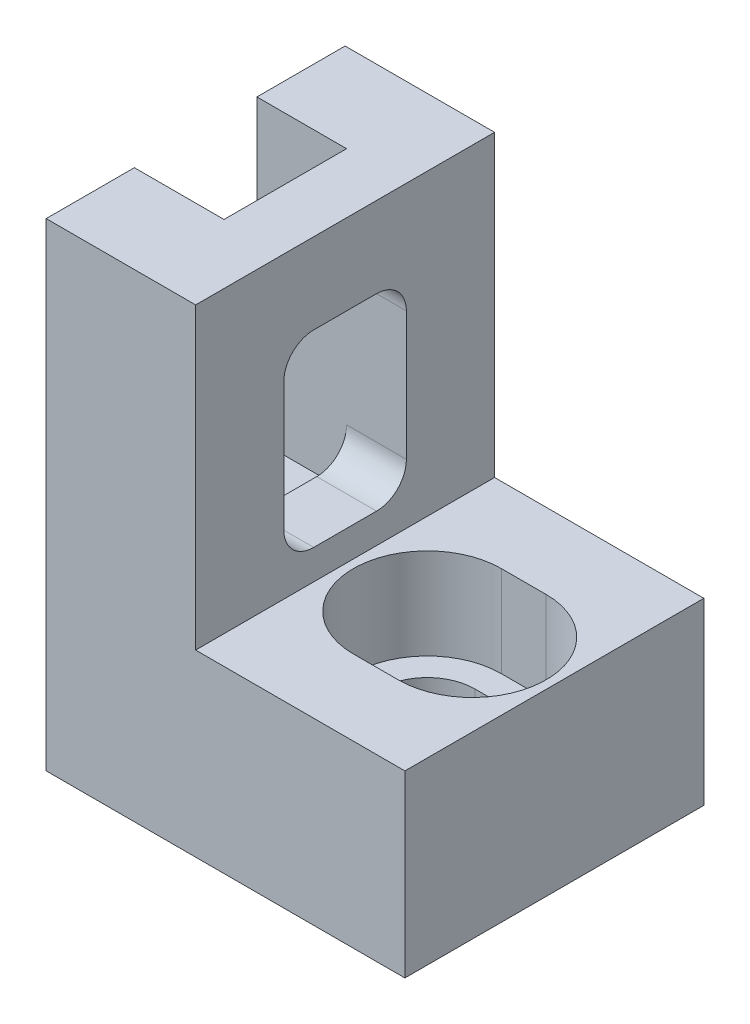
SolidWorks part; units mm, degrees
ref_plane "Front Plane" through (0, 0, 0) normal (0, 0, 1) x (1, 0, 0)
ref_plane "Top Plane" through (0, 0, 0) normal (0, 1, 0) x (1, 0, 0)
ref_plane "Right Plane" through (0, 0, 0) normal (1, 0, 0) x (0, 0, -1)
sketch "Sketch1" plane through (0, 0, 0) normal (1, 0, 0) x (0, 0, -1)
  line L1 (-4.3351, 8.9787) -> (5.6649, 8.9787)
  line L2 (-4.3351, 8.9787) -> (-4.3351, -7.0213)
  line L3 (-4.3351, -7.0213) -> (5.6649, -7.0213)
  line L4 (5.6649, 8.9787) -> (5.6649, -7.0213)
  dimension "D1" = 10
  dimension "D2" = 16
extrude "Boss-Extrude1" add sketch "Sketch1" along normal blind 12
sketch "Sketch2" plane through (0, 0, 4.3351) normal (0, 0, 1) x (1, 0, 0)
  line L0 (12, -7.0213) -> (0, -7.0213) construction
  line L1 (12, 8.9787) -> (5, 8.9787)
  line L2 (12, 8.9787) -> (12, -1.0213)
  line L3 (12, -1.0213) -> (5, -1.0213)
  line L4 (5, 8.9787) -> (5, -1.0213)
  line L5 (0, 8.9787) -> (0, -7.0213) construction
  dimension "D1" = 6
  dimension "D2" = 5
extrude "Cut-Extrude1" cut sketch "Sketch2" against normal through all
sketch "Sketch3" plane through (0, -1.0213, 0) normal (0, 1, 0) x (1, 0, 0)
  line L0 (5, 0.6649) -> (12, 0.6649)
  line L1 (5, 5.6649) -> (5, -4.3351) construction
  line L2 (12, 5.6649) -> (12, -4.3351) construction
  line L3 (9.25, 0.6649) -> (7.75, 0.6649) construction
  line L4 (9.25, -0.9251) -> (7.75, -0.9251)
  line L5 (9.25, 2.2549) -> (7.75, 2.2549)
  line L6 (7.75, 0.6649) -> (9.25, 0.6649) construction
  line L7 (7.75, 3.139) -> (9.25, 3.139)
  line L8 (7.75, -1.8092) -> (9.25, -1.8092)
  line L9 (5, -4.3351) -> (12, -4.3351) construction
  arc A0 (9.25, -0.9251) -> (9.25, 2.2549) centre (9.25, 0.6649) ccw
  arc A1 (7.75, 2.2549) -> (7.75, -0.9251) centre (7.75, 0.6649) ccw
  arc A2 (7.75, 3.139) -> (7.75, -1.8092) centre (7.75, 0.6649) ccw
  arc A3 (9.25, -1.8092) -> (9.25, 3.139) centre (9.25, 0.6649) ccw
  point P8 (8.5, 0.6649)
  point P13 (8.5, 0.6649)
  point P22 (8.5, -4.3351)
  dimension "D1" = 3.18
  dimension "D2" = 4.9482
  dimension "D3" = 1.5
  dimension "D4" = 0
extrude "Cut-Extrude2" cut sketch "Sketch3" against normal through all contours L5 A1 L0 A0 | L0 A1 L4 A0 region at (8.5, -1.0213, -1.3848) region at (8.5, -1.0213, 0.055)
extrude "Cut-Extrude3" cut sketch "Sketch3<3>" against normal blind 3.0448 contours L0 A3 L7 A2 A1 L5 A0 | L8 A3 L0 A0 L4 A1 A2 region at (6.0494, -1.0213, -2.3655) region at (5.718, -1.0213, -0.5958)
sketch "Sketch3<3>" plane through (0, -1.0213, 0) normal (0, 1, 0) x (1, 0, 0) same geometry as "Sketch3"
sketch "Sketch4" plane through (0, 0, 0) normal (-1, 0, 0) x (0, 0, 1)
  line L0 (-5.6649, 8.9787) -> (4.3351, 8.9787) construction
  line L1 (-2.7149, 8.9787) -> (1.3851, 8.9787)
  line L2 (-2.7149, 8.9787) -> (-2.7149, -1.0213)
  line L3 (-2.7149, -1.0213) -> (1.3851, -1.0213)
  line L4 (1.3851, 8.9787) -> (1.3851, -1.0213)
  line L5 (-5.6649, -7.0213) -> (-5.6649, 8.9787) construction
  line L10 (-2.7149, -0.0213) -> (1.3851, -0.0213)
  line L11 (-2.7149, -0.0213) -> (-2.7149, 6.2787)
  line L12 (-2.7149, 6.2787) -> (1.3851, 6.2787)
  line L13 (1.3851, -0.0213) -> (1.3851, 6.2787)
  line L14 (-2.7149, -0.0213) -> (1.3851, 6.2787) construction
  line L15 (-2.7149, 6.2787) -> (1.3851, -0.0213) construction
  line L16 (-5.6649, -0.9462) -> (4.3351, -0.9462)
  line L17 (-5.6649, -0.9462) -> (-5.6649, 1.0538)
  line L18 (-5.6649, 1.0538) -> (4.3351, 1.0538)
  line L19 (4.3351, -0.9462) -> (4.3351, 1.0538)
  line L20 (4.3351, 8.9787) -> (4.3351, -7.0213) construction
  line L21 (4.3351, -7.0213) -> (-5.6649, -7.0213) construction
  point P4 (-0.6649, 8.9787)
  point P7 (-0.6649, 8.9787)
  point P8 (-0.6649, 3.1287)
  line M11 (4.3351, 8.9787) -> (-5.6649, 8.9787)
  dimension "D1" = 0
  dimension "D2" = 4.1
  dimension "D3" = 6.3
  dimension "D4" = 0
  dimension "D5" = 1
  dimension "D6" = 2
  dimension "D7" = 6
extrude "Cut-Extrude4" cut sketch "Sketch4" against normal through all contours L12 L2 L10 L4 | L18 L11 L10 L13 region at (0, 3.6663, -0.6649) region at (0, 0.5163, -0.6649)
fillet "Fillet2" radius 1 4 edges at (2.5, -0.0213, 1.3851) (2.5, 6.2787, 1.3851) (2.5, 6.2787, -2.7149) (2.5, -0.0213, -2.7149)
extrude "Cut-Extrude7" cut sketch "Sketch4<6>" against normal blind 3 contours L2 L12 L4 M11 | L10 L2 L3 L4 | L18 L11 L10 L13 | L2 L18 L4 L12 region at (0, 7.6287, -0.6649) region at (0, 3.6663, -0.6649) region at (0, 0.5163, -0.6649) region at (0, -0.4837, -0.6649)
sketch "Sketch4<6>" plane through (0, 0, 0) normal (-1, 0, 0) x (0, 0, 1) same geometry as "Sketch4"
